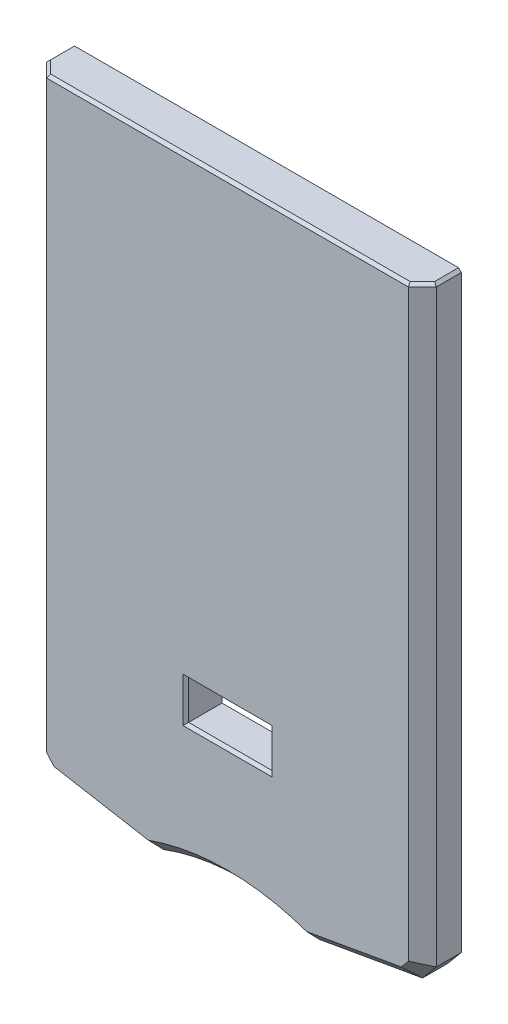
SolidWorks part; units mm, degrees
ref_plane "Front Plane" through (0, 0, 0) normal (0, 0, 1) x (1, 0, 0)
ref_plane "Top Plane" through (0, 0, 0) normal (0, 1, 0) x (1, 0, 0)
ref_plane "Right Plane" through (0, 0, 0) normal (1, 0, 0) x (0, 0, -1)
sketch "Sketch1" plane through (0, 0, 0) normal (0, 0, 1) x (1, 0, 0)
  line L0 (-35, 35) -> (35, 35)
  line L1 (-35, 0) -> (35, 0)
  line L2 (-35, 43.6714) -> (-35, 150)
  line L3 (-35, 150) -> (35, 150)
  line L4 (35, 43.6714) -> (35, 150)
  line L5 (-35, 0) -> (35, 150) construction
  line L6 (-35, 150) -> (35, 0) construction
  line L7 (0, 35) -> (-35, 41.1714) construction
  line L8 (-32.538, 40.7373) -> (-14.0026, 37.469)
  line L9 (0, 35) -> (0, 58.9879) construction
  line L10 (32.538, 40.7373) -> (14.0026, 37.469)
  line L11 (-35, 43.6714) -> (-32.538, 40.7373)
  line L12 (35, 43.6714) -> (32.538, 40.7373)
  line L14 (-7.5, 61.5) -> (7.5, 61.5)
  line L15 (-7.5, 61.5) -> (-7.5, 68.5)
  line L16 (-7.5, 68.5) -> (7.5, 68.5)
  line L17 (7.5, 61.5) -> (7.5, 68.5)
  line L18 (-7.5, 61.5) -> (7.5, 68.5) construction
  line L19 (-7.5, 68.5) -> (7.5, 61.5) construction
  circle A0 centre (0, 0) radius 40
  point P7 (0, 75)
  point P14 (35, 41.1714)
  point P20 (0, 65)
  dimension "D1" = 80
  dimension "D2" = 150
  dimension "D3" = 70
  dimension "D4" = 35
  dimension "D5" = 10
  dimension "D6" = 7
  dimension "D7" = 15
  dimension "D8" = 30
extrude "Boss-Extrude1" add sketch "Sketch1" along normal blind 7 contours A0 L10 L4 L3 L2 L8 region at (0, 95.075, 0)
chamfer "2,5mm Chamfer" distance 2.5 angle 45 7 edges at (-35, 96.8357, 7) (-23.2703, 39.1032, 7) (0, 40, 7) (23.2703, 39.1032, 7) (35, 96.8357, 7) (-33.769, 42.2044, 7) (33.769, 42.2044, 7)
chamfer "0,5mm Chamfer" distance 0.5 angle 45 13 edges at (35, 150, 2.25) (33.75, 150, 5.75) (0, 150, 7) (-33.75, 150, 5.75) (-35, 150, 2.25) (0, 61.5, 7) (7.5, 65, 7) (0, 68.5, 7) (-7.5, 65, 7) (0, 61.5, 0) (-7.5, 65, 0) (0, 68.5, 0) (7.5, 65, 0)
